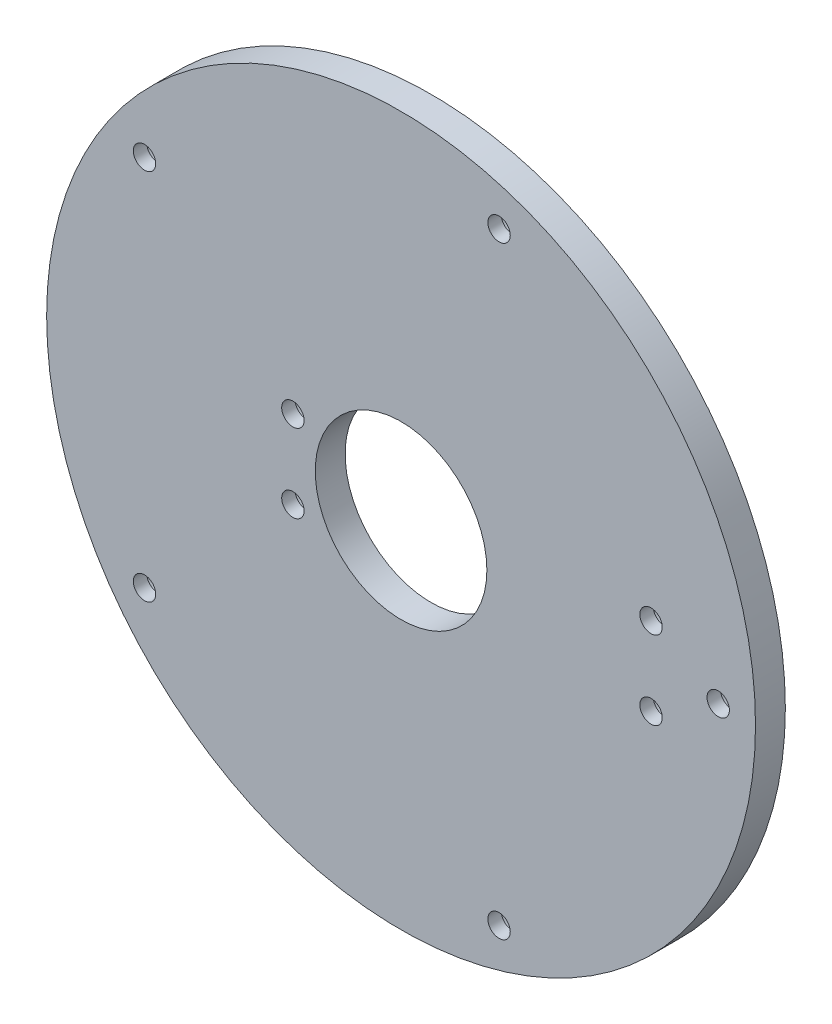
SolidWorks part; units mm, degrees
material "Beech"
ref_plane "Front Plane" through (0, 0, 0) normal (0, 0, 1) x (1, 0, 0)
ref_plane "Top Plane" through (0, 0, 0) normal (0, 1, 0) x (1, 0, 0)
ref_plane "Right Plane" through (0, 0, 0) normal (1, 0, 0) x (0, 0, -1)
sketch "Sketch1" plane through (0, 0, 0) normal (0, 0, 1) x (1, 0, 0)
  circle A0 centre (90, 47.5) radius 1.5
  circle A1 centre (60.6332, 87.9199) radius 1.5
  circle A2 centre (13.1168, 72.4809) radius 1.5
  circle A3 centre (13.1168, 22.5191) radius 1.5
  circle A4 centre (60.6332, 7.0801) radius 1.5
  circle A5 centre (47.5, 47.5) radius 47.5
  circle A6 centre (47.5, 47.5) radius 11.5
  circle A7 centre (81, 52.625) radius 1.5
  circle A8 centre (81, 42.125) radius 1.5
  circle A9 centre (33, 52.625) radius 1.5
  circle A10 centre (33, 42.125) radius 1.5
  circle A11 centre (13.1168, 22.5191) radius 2.75
  circle A12 centre (60.6332, 7.0801) radius 2.75
  circle A13 centre (33, 42.125) radius 2.75
  circle A14 centre (33, 52.625) radius 2.75
  circle A15 centre (13.1168, 72.4809) radius 2.75
  circle A16 centre (60.6332, 87.9199) radius 2.75
  circle A17 centre (81, 52.625) radius 2.75
  circle A18 centre (90, 47.5) radius 2.75
  circle A19 centre (81, 42.125) radius 2.75
extrude "Boss-Extrude2" add sketch "Sketch1" along normal blind 4 contours A5 A19 A18 A17 A16 A15 A14 A13 A12 A11 A6 | A15 A2 | A16 A1 | A14 A9 | A17 A7 | A18 A0 | A19 A8 | A13 A10 | A11 A3 | A12 A4 region at (1.3435, 47.5, 0) region at (10.4446, 22.5191, 0) region at (57.961, 7.0801, 0) region at (30.3278, 42.125, 0) region at (30.3278, 52.625, 0) region at (10.4446, 72.4809, 0) region at (57.961, 87.9199, 0) region at (78.3278, 52.625, 0) region at (87.3278, 47.5, 0) region at (78.3278, 42.125, 0)
extrude "Cut-Extrude1" cut sketch "Sketch1<5>" along normal blind 2.2 contours A14 A9 | A13 A10 | A11 A3 | A15 A2 | A16 A1 | A17 A7 | A18 A0 | A19 A8 | A12 A4 region at (10.4446, 22.5191, 0) region at (57.961, 7.0801, 0) region at (30.3278, 42.125, 0) region at (30.3278, 52.625, 0) region at (10.4446, 72.4809, 0) region at (57.961, 87.9199, 0) region at (78.3278, 52.625, 0) region at (87.3278, 47.5, 0) region at (78.3278, 42.125, 0)
sketch "Sketch1<5>" plane through (0, 0, 0) normal (0, 0, 1) x (1, 0, 0) same geometry as "Sketch1"
